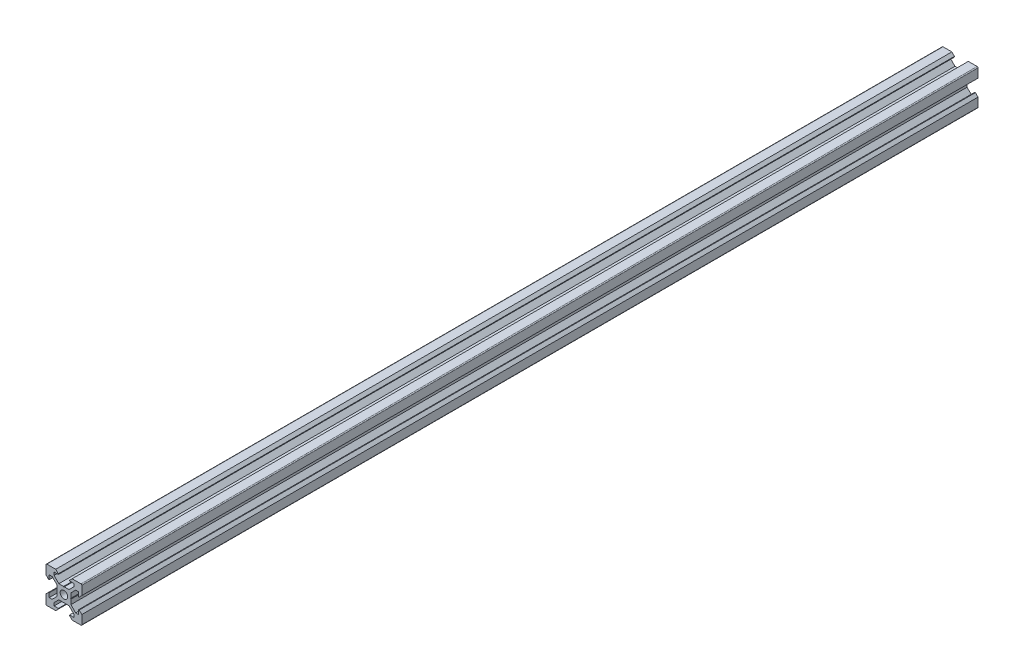
SolidWorks part; units mm, degrees
material "6061-T6 (SS)"
ref_plane "Front Plane" through (0, 0, 0) normal (0, 0, 1) x (1, 0, 0)
ref_plane "Top Plane" through (0, 0, 0) normal (0, 1, 0) x (1, 0, 0)
ref_plane "Right Plane" through (0, 0, 0) normal (1, 0, 0) x (0, 0, -1)
sketch "Sketch1" plane through (0, 0, 0) normal (0, 0, 1) x (1, 0, 0)
  line L1 (9.5, -10) -> (-9.5, -10)
  line L2 (10, -9.5) -> (10, 9.5)
  line L3 (9.5, 10) -> (-9.5, 10)
  line L4 (-10, -9.5) -> (-10, 9.5)
  line L5 (10, -10) -> (-10, 10) construction
  line L6 (10, 10) -> (-10, -10) construction
  circle A0 centre (0, 0) radius 2.1
  arc A1 (-9.5, 10) -> (-10, 9.5) centre (-9.5, 9.5) ccw
  arc A2 (10, 9.5) -> (9.5, 10) centre (9.5, 9.5) ccw
  arc A3 (9.5, -10) -> (10, -9.5) centre (9.5, -9.5) ccw
  arc A4 (-9.5, -10) -> (-10, -9.5) centre (-9.5, -9.5) cw
  point P0 (0, 0)
  line B0 (0, 0) -> (0, 10) construction
  line B1 (0, 3.69) -> (-0.21, 3.9)
  line B2 (-0.21, 3.9) -> (-2.8393, 3.9)
  line B3 (-2.8393, 3.9) -> (-5.5, 6.5607)
  line B4 (-5.5, 6.5607) -> (-5.5, 8.2)
  line B5 (-5.5, 8.2) -> (-3.125, 8.2)
  line B6 (-3.125, 8.2) -> (-3.125, 8.545)
  line B7 (-3.125, 8.545) -> (-4.58, 10)
  line B8 (-4.58, 10) -> (4.58, 10)
  line B9 (0, 0) -> (-5.9132, 5.9132) construction
  line B10 (3.125, 8.545) -> (4.58, 10)
  line B11 (3.125, 8.2) -> (3.125, 8.545)
  line B12 (5.5, 8.2) -> (3.125, 8.2)
  line B13 (5.5, 6.5607) -> (5.5, 8.2)
  line B14 (2.8393, 3.9) -> (5.5, 6.5607)
  line B15 (0.21, 3.9) -> (2.8393, 3.9)
  line B16 (0, 3.69) -> (0.21, 3.9)
  line B17 (0, 0) -> (-10, 0) construction
  line B18 (-3.69, 0) -> (-3.9, -0.21)
  line B19 (-3.9, -0.21) -> (-3.9, -2.8393)
  line B20 (-3.9, -2.8393) -> (-6.5607, -5.5)
  line B21 (-6.5607, -5.5) -> (-8.2, -5.5)
  line B22 (-8.2, -5.5) -> (-8.2, -3.125)
  line B23 (-8.2, -3.125) -> (-8.545, -3.125)
  line B24 (-8.545, -3.125) -> (-10, -4.58)
  line B25 (-10, -4.58) -> (-10, 4.58)
  line B26 (0, 0) -> (-5.9132, -5.9132) construction
  line B27 (-8.545, 3.125) -> (-10, 4.58)
  line B28 (-8.2, 3.125) -> (-8.545, 3.125)
  line B29 (-8.2, 5.5) -> (-8.2, 3.125)
  line B30 (-6.5607, 5.5) -> (-8.2, 5.5)
  line B31 (-3.9, 2.8393) -> (-6.5607, 5.5)
  line B32 (-3.9, 0.21) -> (-3.9, 2.8393)
  line B33 (-3.69, 0) -> (-3.9, 0.21)
  line B34 (0, 0) -> (0, -10) construction
  line B35 (0, -3.69) -> (0.21, -3.9)
  line B36 (0.21, -3.9) -> (2.8393, -3.9)
  line B37 (2.8393, -3.9) -> (5.5, -6.5607)
  line B38 (5.5, -6.5607) -> (5.5, -8.2)
  line B39 (5.5, -8.2) -> (3.125, -8.2)
  line B40 (3.125, -8.2) -> (3.125, -8.545)
  line B41 (3.125, -8.545) -> (4.58, -10)
  line B42 (4.58, -10) -> (-4.58, -10)
  line B43 (0, 0) -> (5.9132, -5.9132) construction
  line B44 (-3.125, -8.545) -> (-4.58, -10)
  line B45 (-3.125, -8.2) -> (-3.125, -8.545)
  line B46 (-5.5, -8.2) -> (-3.125, -8.2)
  line B47 (-5.5, -6.5607) -> (-5.5, -8.2)
  line B48 (-2.8393, -3.9) -> (-5.5, -6.5607)
  line B49 (-0.21, -3.9) -> (-2.8393, -3.9)
  line B50 (0, -3.69) -> (-0.21, -3.9)
  line B51 (0, 0) -> (10, 0) construction
  line B52 (3.69, 0) -> (3.9, 0.21)
  line B53 (3.9, 0.21) -> (3.9, 2.8393)
  line B54 (3.9, 2.8393) -> (6.5607, 5.5)
  line B55 (6.5607, 5.5) -> (8.2, 5.5)
  line B56 (8.2, 5.5) -> (8.2, 3.125)
  line B57 (8.2, 3.125) -> (8.545, 3.125)
  line B58 (8.545, 3.125) -> (10, 4.58)
  line B59 (10, 4.58) -> (10, -4.58)
  line B60 (0, 0) -> (5.9132, 5.9132) construction
  line B61 (8.545, -3.125) -> (10, -4.58)
  line B62 (8.2, -3.125) -> (8.545, -3.125)
  line B63 (8.2, -5.5) -> (8.2, -3.125)
  line B64 (6.5607, -5.5) -> (8.2, -5.5)
  line B65 (3.9, -2.8393) -> (6.5607, -5.5)
  line B66 (3.9, -0.21) -> (3.9, -2.8393)
  line B67 (3.69, 0) -> (3.9, -0.21)
  dimension "D1" = 4.2
  dimension "D3" = 0.5
  dimension "D2" = 20
sketch_block_instance "V Slot 1-4"
sketch_block "V Slot 1" parameters "D1"=10, "D2"=11, "D3"=4.3, "D4"=1.8, "D5"=0.21, "D6"=45, "D7"=9.16, "D8"=1.5, "D9"=6.25
sketch_block_instance "V Slot 1-5"
sketch_block_instance "V Slot 1-6"
sketch_block_instance "V Slot 1-7"
extrude "Boss-Extrude1" add sketch "Sketch1" along normal blind 500 contours B67 B52 B53 B54 B55 B56 B57 B58 L2 A2 L3 B10 B11 B12 B13 B14 B15 B16 B1 B2 B3 B4 B5 B6 B7 A1 L4 B27 B28 B29 B30 B31 B32 B33 B18 B19 B20 B21 B22 B23 B24 A4 L1 B44 B45 B46 B47 B48 B49 region at (7.04, -9.7172, 0)
